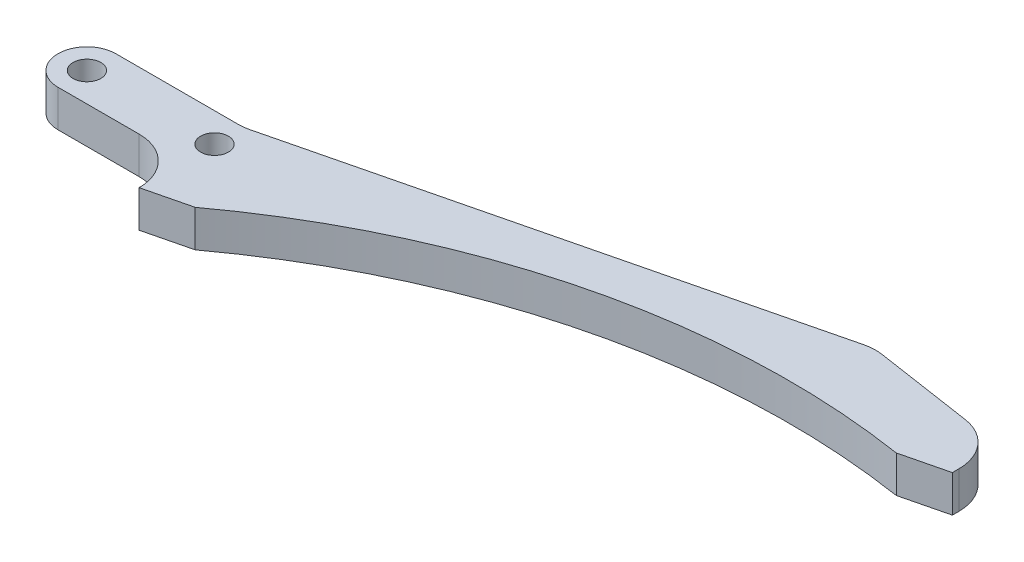
SolidWorks part; units mm, degrees
ref_plane "前视基准面" through (0, 0, 0) normal (0, 0, 1) x (1, 0, 0)
ref_plane "上视基准面" through (0, 0, 0) normal (0, 1, 0) x (1, 0, 0)
ref_plane "右视基准面" through (0, 0, 0) normal (1, 0, 0) x (0, 0, -1)
other "Configuration Table"
sketch "草图1" plane through (0, 0, 0) normal (0, 1, 0) x (1, 0, 0)
  line L0 (0, 0) -> (-22, 0) construction
  line L1 (0, 0) -> (11, 0) construction
  line L2 (-16, 5) -> (16, 5)
  line L3 (-16, 5) -> (-16, -5)
  line L4 (-16, -5) -> (16, -5)
  line L5 (16, 5) -> (16, -5)
  line L6 (-16, 5) -> (16, -5) construction
  line L7 (-16, -5) -> (16, 5) construction
  line L8 (11, 0) -> (-11, 0) construction
  circle A0 centre (11, 0) radius 2.395
  circle A1 centre (-11, 0) radius 2.395
  dimension "D6" = 4.79
  dimension "D7" = 4.79
  dimension "D1" = 22
  dimension "D2" = 10
  dimension "D3" = 32
  dimension "D4" = 11
  dimension "D5" = 22
extrude "凸台-拉伸2" add sketch "草图1" along normal blind 6.36
fillet "圆角4" radius 5 2 edges at (-16, 3.18, 5) (-16, 3.18, -5)
sketch "草图2" plane through (0, 0, 0) normal (0, 1, 0) x (1, 0, 0)
  line L0 (11, 2.395) -> (11, 5) construction
  line L1 (16, 5) -> (-11, 5) construction
  line L2 (11, 5) -> (11, -5) construction
  line L3 (-11, -5) -> (16, -5) construction
  line L4 (11, -5) -> (11, -13) construction
  line L5 (11, 5) -> (98.4213, 26.3898)
  line L6 (11, 5) -> (16, 0)
  line L7 (16, -5) -> (16, 5) construction
  line L8 (16, 0) -> (11, -5)
  line L9 (11, -5) -> (11, -13)
  line L10 (11, -13) -> (18.7708, -11.0987)
  line L11 (18.7708, -11.0987) -> (115.9055, 12.6677)
  line L12 (115.9055, 12.6677) -> (123.6763, 14.569)
  line L13 (123.6763, 14.569) -> (123.6763, 22.569)
  line L14 (123.6763, 22.569) -> (98.4213, 26.3898)
  circle A0 centre (11, 0) radius 2.395 construction
  dimension "D1" = 8
  dimension "D2" = 90
  dimension "D3" = 8
  dimension "D4" = 100
  dimension "D5" = 8
  dimension "D6" = 8
extrude "凸台-拉伸3" add sketch "草图2" along normal up to surface (6.36 mm away) up to face at (11, 6.36, 2.395)
fillet "圆角5" radius 8 2 edges at (123.6763, 3.18, -22.569) (11, 3.18, 5)
fillet "圆角6" radius 8 2 edges at (11, 3.18, -5) (98.4213, 3.18, -26.3898)
sketch "草图3" plane through (0, 0, 0) normal (0, 1, 0) x (1, 0, 0)
  line L0 (11, -13) -> (123.6763, 14.569) construction
  line L1 (67.3381, 0.7845) -> (86.3513, -76.9233) construction
  line L2 (11, -13) -> (18.7708, -11.0987) construction
  line L3 (18.7708, -11.0987) -> (115.9055, 12.6677) construction
  line L4 (86.3513, -76.9233) -> (91.1046, -96.3502) construction
  line L5 (91.1046, -96.3502) -> (95.8578, -115.7772) construction
  circle A0 centre (95.8578, -115.7772) radius 130
  dimension "D4" = 20
  dimension "D5" = 20
  dimension "D1" = 80
  dimension "D2" = 8
  dimension "D3" = 100
extrude "切除-拉伸2" cut sketch "草图3" along normal up to surface (6.36 mm away) up to face at (46.6767, 6.36, -8.4388)
